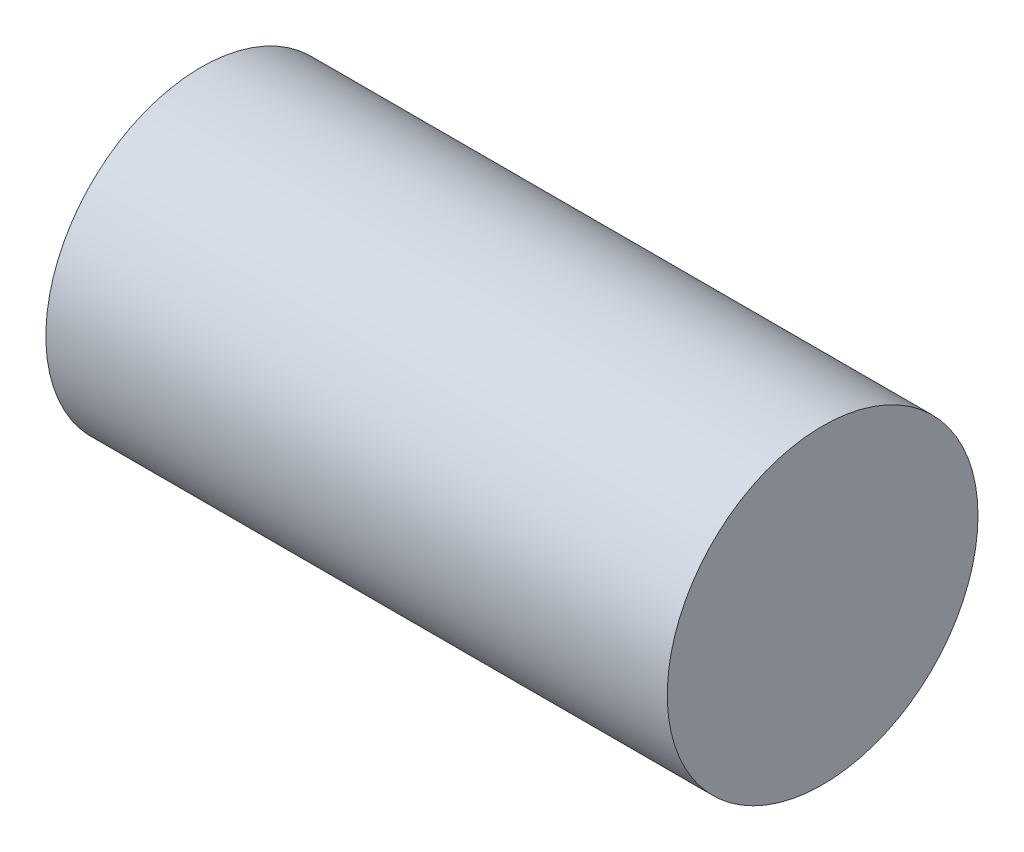
SolidWorks part; units mm, degrees
ref_plane "前视基准面" through (0, 0, 0) normal (0, 0, 1) x (1, 0, 0)
ref_plane "上视基准面" through (0, 0, 0) normal (0, 1, 0) x (1, 0, 0)
ref_plane "右视基准面" through (0, 0, 0) normal (1, 0, 0) x (0, 0, -1)
other "Configuration Table"
sketch "Sketch1" plane through (0, 0, 0) normal (1, 0, 0) x (0, 0, -1)
  circle A0 centre (0, 0) radius 20
extrude "Boss-Extrude1" add sketch "Sketch1" along normal blind 80
sketch3d "3DSketch1"
  line L0 (0, 0, -100) -> (0, 0, 100) construction
ref_axis "Axis_Joint" through (0, 0, -100) along (0, 0, 1)
sketch3d "3DSketch2"
  line L0 (0, 0, 0) -> (0, 0, 100) construction
ref_axis "Axis_Rotate" through (0, 0, 0) along (0, 0, 1)
ref_plane "Mate_Base" through (0, 0, 0) normal (1, 0, 0) x (0, 0, -1)
ref_plane "Mate_End" through (80, 0, 0) normal (1, 0, 0) x (0, 0, -1)
